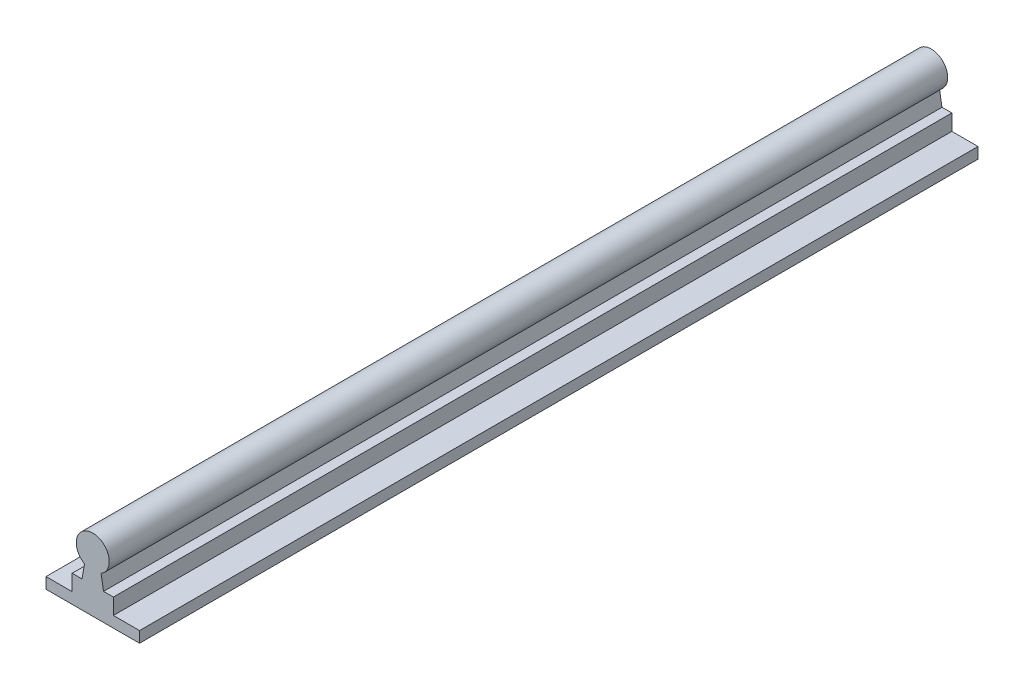
SolidWorks part; units mm, degrees
material "Chrome Stainless Steel"
ref_plane "Front Plane" through (0, 0, 0) normal (0, 0, 1) x (1, 0, 0)
ref_plane "Top Plane" through (0, 0, 0) normal (0, 1, 0) x (1, 0, 0)
ref_plane "Right Plane" through (0, 0, 0) normal (1, 0, 0) x (0, 0, -1)
sketch "Sketch1" plane through (0, 0, 0) normal (0, 0, 1) x (1, 0, 0)
  line L0 (21.3075, 0) -> (-12.6925, 0)
  line L1 (21.3075, 0) -> (21.3075, 4)
  line L2 (21.3075, 4) -> (11.8075, 4)
  line L3 (11.8075, 4) -> (11.8075, 9.8)
  line L4 (11.8075, 9.8) -> (8.2244, 9.8)
  line L5 (8.2244, 9.8) -> (7.3075, 15)
  line L6 (4.3075, 0) -> (4.3075, 36.0795) construction
  line L7 (0.3906, 9.8) -> (1.3075, 15)
  line L8 (-3.1925, 9.8) -> (0.3906, 9.8)
  line L9 (-3.1925, 4) -> (-3.1925, 9.8)
  line L10 (-12.6925, 0) -> (-12.6925, 4)
  line L11 (-12.6925, 4) -> (-3.1925, 4)
  arc A0 (7.3075, 15) -> (1.3075, 15) centre (4.3075, 20.1962) ccw
  point P17 (4.3075, 0)
  dimension "D5" = 6
  dimension "D1" = 17
  dimension "D2" = 4
  dimension "D3" = 9.8
  dimension "D4" = 15
  dimension "D6" = 3
  dimension "D8" = 20.1962
  dimension "D9" = 7.5
extrude "Boss-Extrude1" add sketch "Sketch1" along normal blind 304.8
